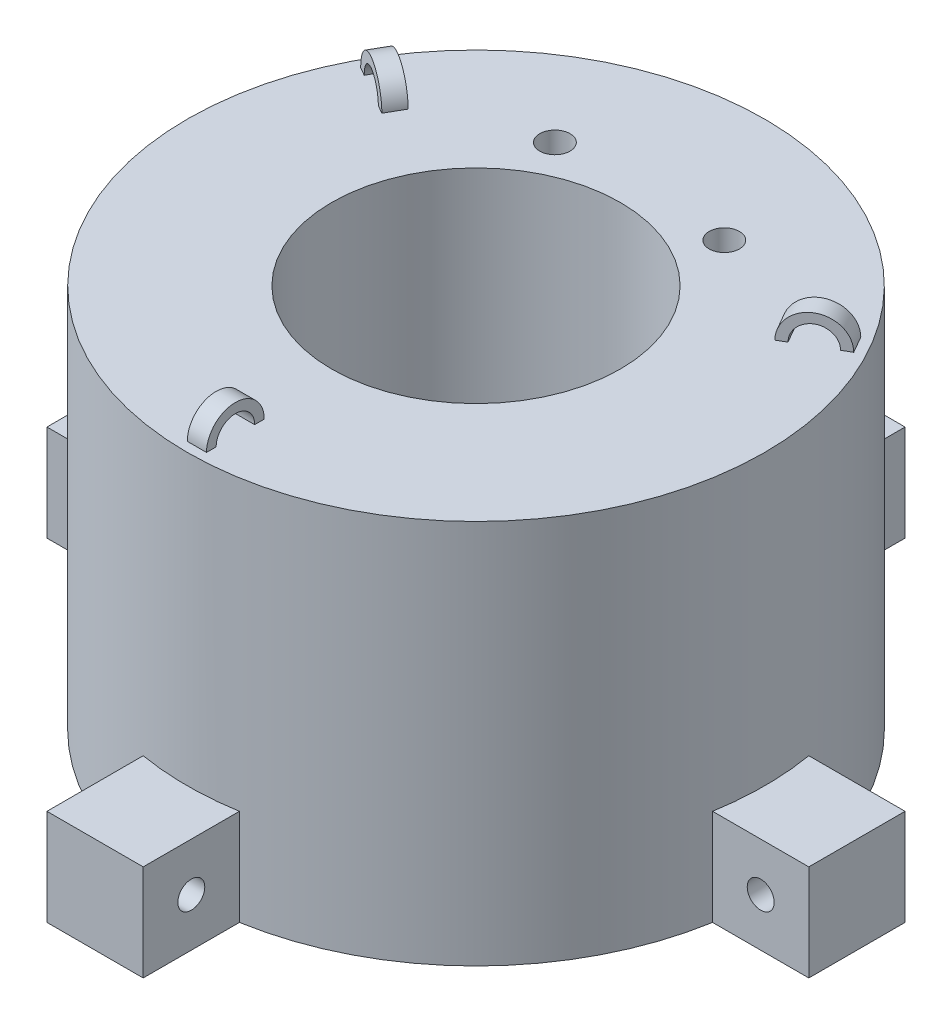
SolidWorks part; units mm, degrees
ref_plane "Front Plane" through (0, 0, 0) normal (0, 0, 1) x (1, 0, 0)
ref_plane "Top Plane" through (0, 0, 0) normal (0, 1, 0) x (1, 0, 0)
ref_plane "Right Plane" through (0, 0, 0) normal (1, 0, 0) x (0, 0, -1)
sketch "Sketch2" plane through (0, 0, 0) normal (0, 1, 0) x (1, 0, 0)
  circle A0 centre (0, 0) radius 38.1
  dimension "D1" = 76.2
extrude "Boss-Extrude1" add sketch "Sketch2" along normal blind 50.8
sketch "Sketch3" plane through (0, 50.8, 0) normal (0, 1, 0) x (1, 0, 0)
  circle A0 centre (0, 0) radius 19.05
  dimension "D1" = 38.1
extrude "Cut-Extrude1" cut sketch "Sketch3" against normal blind 76.2
sketch "Sketch4" plane through (0, 0, 0) normal (0, 1, 0) x (1, 0, 0)
  line L1 (-50.2671, 6.35) -> (-50.2671, -6.35)
  line L2 (-50.2671, -6.35) -> (-37.5671, -6.35)
  line L3 (-50.2671, 6.35) -> (-37.5671, 6.35)
  circle A2 centre (0, 0) radius 38.1 construction
  arc A3 (-37.5671, -6.35) -> (-37.5671, 6.35) centre (0, 0) cw
  dimension "D1" = 12.7
  dimension "D2" = 12.7
  dimension "D3" = 12.7
extrude "Boss-Extrude2" add sketch "Sketch4" along normal blind 12.7
sketch "Sketch5" plane through (0, 0, 6.35) normal (0, 0, 1) x (1, 0, 0)
  line L0 (-50.2671, 12.7) -> (-37.5671, 12.7) construction
  line L1 (-50.2671, 12.7) -> (-50.2671, 0) construction
  circle A0 centre (-43.9171, 6.35) radius 1.778
  point P4 (-43.9171, 12.7)
  point P7 (-50.2671, 6.35)
  dimension "D1" = 3.556
extrude "Cut-Extrude2" cut sketch "Sketch5" against normal blind 25.4
pattern_circular "CirPattern2" count 4 over 360 about axis through (0, 50.8, 0) along (0, -1, 0) of "Boss-Extrude2", "Cut-Extrude2" reverse direction yes
sketch "Sketch10" plane through (0, 50.8, 0) normal (0, 1, 0) x (1, 0, 0)
  line L0 (0, 0) -> (-32.9956, 19.05) construction
  line L1 (0, 0) -> (32.9956, 19.05) construction
  line L2 (0, 0) -> (0, -38.1) construction
  circle A0 centre (11.176, 21.59) radius 2
  circle A2 centre (0, 0) radius 38.1 construction
  arc A3 (-6.35, -37.5671) -> (6.35, -37.5671) centre (0, 0) ccw construction
  point P7 (32.9956, 19.05)
  dimension "D1" = 21.59
  dimension "D3" = 4
  dimension "D2" = 11.176
  dimension "D4" = 120
  dimension "D5" = 120
extrude "Cut-Extrude4" cut sketch "Sketch10" against normal blind 12.7
mirror "Mirror1" about plane through (0, 0, 0) normal (1, 0, 0) of "Cut-Extrude4"
ref_plane "Plane1" through (0, 0, 0) normal (0.5, 0, 0.866) x (0.866, 0, -0.5)
sketch "Sketch13" plane through (0, 0, 0) normal (0.5, 0, 0.866) x (0.866, 0, -0.5)
  line L0 (36.83, 50.8) -> (29.21, 50.8)
  line L1 (0, 50.8) -> (38.1, 50.8) construction
  line L2 (30.48, 50.8) -> (35.56, 50.8)
  arc A0 (29.21, 50.8) -> (36.83, 50.8) centre (33.02, 50.8) cw
  arc A1 (35.56, 50.8) -> (30.48, 50.8) centre (33.02, 50.8) ccw
  point P9 (38.1, 50.8)
  point P10 (36.7691, 50.8594)
  dimension "D1" = 3.81
  dimension "D2" = 2.54
  dimension "D3" = 1.27
extrude "Boss-Extrude5" add sketch "Sketch13" along normal blind 1.27 and the other way blind 1.27 contours A1 L0 A0 region at (31.3458, 50.8852, -18.0975)
pattern_circular "CirPattern3" count 3 over 360 about axis through (0, -25.4, 0) along (0, 1, 0) of "Boss-Extrude5" reverse direction yes
